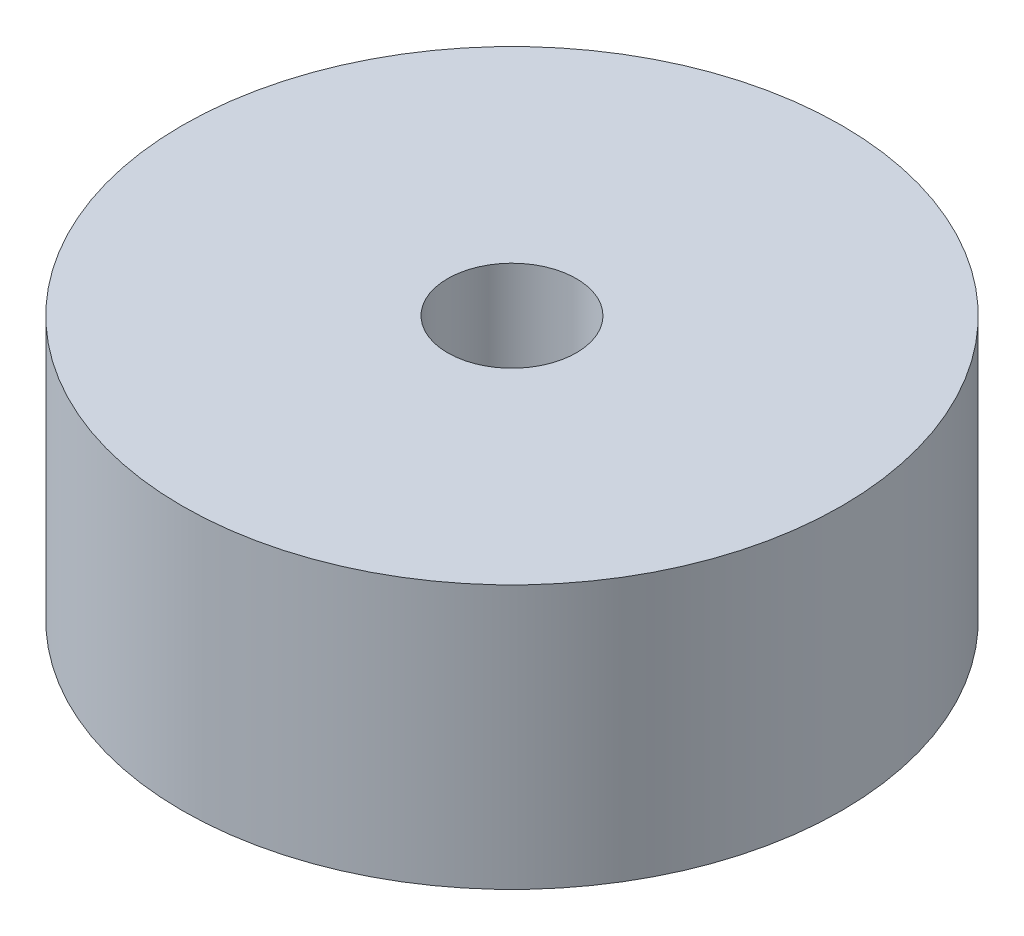
SolidWorks part; units mm, degrees
ref_plane "Front" through (0, 0, 0) normal (0, 0, 1) x (1, 0, 0)
ref_plane "Top" through (0, 0, 0) normal (0, 1, 0) x (1, 0, 0)
ref_plane "Right" through (0, 0, 0) normal (1, 0, 0) x (0, 0, -1)
sketch "Sketch1" plane through (0, 0, 0) normal (0, 1, 0) x (1, 0, 0)
  circle A0 centre (0, 0) radius 7.9375
  circle A1 centre (0, 0) radius 1.5494
  dimension "D1" = 15.875
  dimension "D2" = 3.0988
extrude "Boss-Extrude1" add sketch "Sketch1" along normal blind 6.35
